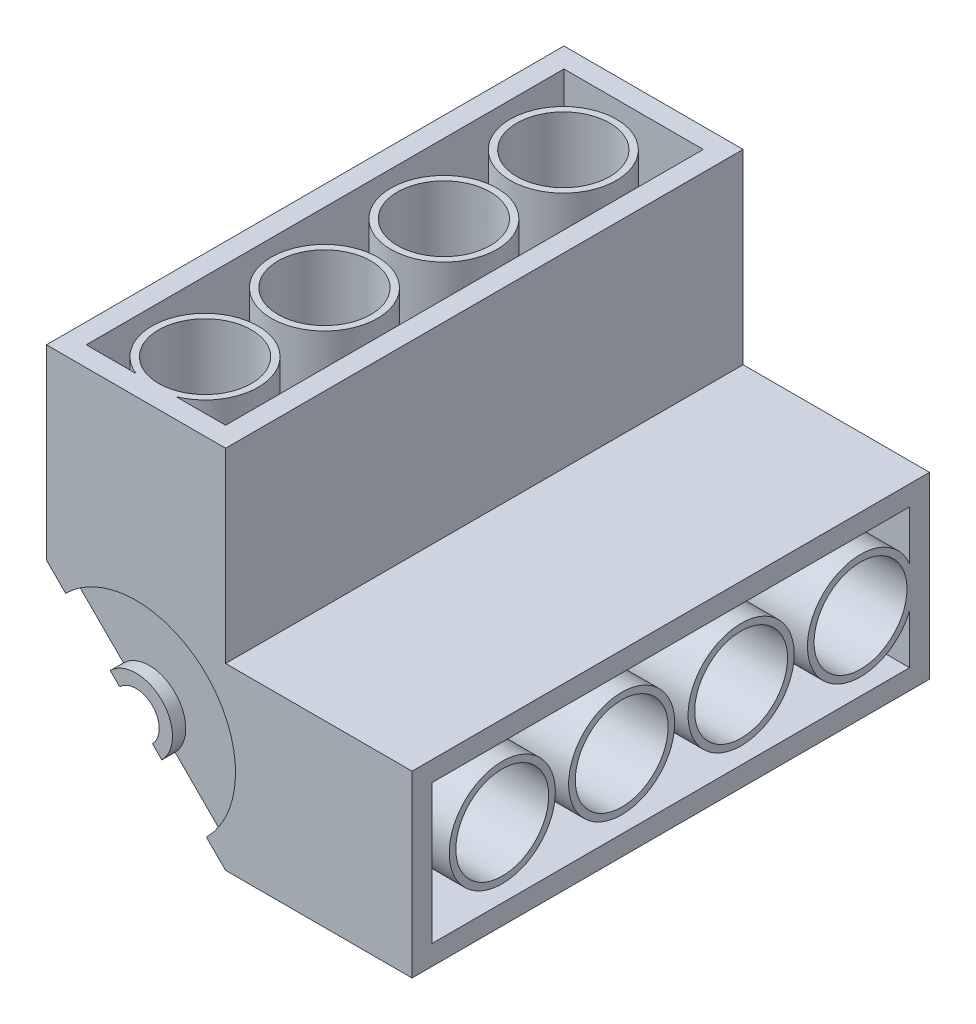
SolidWorks part; units mm, degrees
ref_plane "Alzado" through (0, 0, 0) normal (0, 0, 1) x (1, 0, 0)
ref_plane "Planta" through (0, 0, 0) normal (0, 1, 0) x (1, 0, 0)
ref_plane "Vista lateral" through (0, 0, 0) normal (1, 0, 0) x (0, 0, -1)
sketch "Croquis1" plane through (0, 0, 0) normal (0, 0, 1) x (1, 0, 0)
  line L0 (-81.5266, -99.9092) -> (138.4734, -99.9092) construction
  line L1 (-67.5, 67.5) -> (-12.3744, 12.3744)
  line L2 (12.3744, -12.3744) -> (67.5, -67.5)
  line L3 (-67.5, 67.5) -> (-67.5, 208)
  line L4 (-67.5, 208) -> (67.5, 208)
  line L5 (67.5, 208) -> (67.5, 67.5)
  line L6 (67.5, 67.5) -> (208, 67.5)
  line L7 (208, 67.5) -> (208, -67.5)
  line L8 (208, -67.5) -> (67.5, -67.5)
  arc A0 (12.3744, -12.3744) -> (-12.3744, 12.3744) centre (0, 0) ccw
  arc A1 (53.033, -53.033) -> (-53.033, 53.033) centre (0, 0) ccw
  arc A2 (19.4454, -19.4454) -> (-19.4454, 19.4454) centre (0, 0) ccw
  dimension "D1" = 35
  dimension "D2" = 55
  dimension "D3" = 150
  dimension "D4" = 45
  dimension "D5" = 208
  dimension "D6" = 135
  dimension "D7" = 275.5
extrude "Saliente-Extruir4" add sketch "Croquis1" along normal blind 390 contours A1 L2 L8 L7 L6 L5 L4 L3 L1 region at (-63.6038, 137.75, 0)
ref_plane "Plano2" through (0, 0, 10) normal (0, 0, -1) x (-1, 0, 0)
extrude "Saliente-Extruir5" add sketch "Croquis1<7>" along normal blind 10 from surface contours A2 L2 A1 L1 region at (24.7221, 24.7221, 0) starting at plane "Plano2"
sketch "Croquis1<7>" plane through (0, 0, 0) normal (0, 0, 1) x (1, 0, 0) same geometry as "Croquis1"
extrude "Saliente-Extruir6" add sketch "Croquis1<8>" along normal blind 30 contours L2 A2 L1 A0 region at (18.976, 18.976, 0)
sketch "Croquis1<8>" plane through (0, 0, 0) normal (0, 0, 1) x (1, 0, 0) same geometry as "Croquis1"
pattern_linear "MatrizL1" count 5 spacing 90 along (0, 0, 1) of "Saliente-Extruir5", "Saliente-Extruir6"
sketch "Croquis6" plane through (208, 0, 0) normal (1, 0, 0) x (0, 0, -1)
  line L0 (-390, 67.5) -> (0, 67.5) construction
  line L1 (-375, -52.5) -> (-15, -52.5)
  line L2 (-375, -52.5) -> (-375, 52.5)
  line L3 (-375, 52.5) -> (-15, 52.5)
  line L4 (-15, -52.5) -> (-15, 52.5)
  line L5 (-375, -52.5) -> (-15, 52.5) construction
  line L6 (-375, 52.5) -> (-15, -52.5) construction
  line L7 (0, 67.5) -> (0, -67.5) construction
  point P0 (-195, 0)
  dimension "D1" = 105
  dimension "D2" = 360
  dimension "D3" = 15
  dimension "D4" = 15
extrude "Cortar-Extruir2" cut sketch "Croquis6" against normal blind 120
sketch "Croquis8" plane through (208, 0, 0) normal (1, 0, 0) x (0, 0, -1)
  line L0 (-390, 0) -> (-338, 0) construction
  line L2 (-390, 67.5) -> (-390, -67.5) construction
  circle A0 centre (-338, 0) radius 40
  circle A1 centre (-338, 0) radius 35
  dimension "D2" = 80
  dimension "D3" = 70
  dimension "D1" = 52
ref_plane "Plano4" through (0, 0, 0) normal (0.7071, -0.7071, 0) x (0, 0, -1)
mirror "Simetría2" about plane through (0, 0, 0) normal (0.7071, -0.7071, 0) of "Cortar-Extruir2"
sketch "Croquis16" plane through (208, 0, 0) normal (1, 0, 0) x (0, 0, -1)
  line L0 (0, 67.5) -> (0, -67.5) construction
  circle A0 centre (-52, 0) radius 35
  dimension "D2" = 70
  dimension "D1" = 52
extrude "Cortar-Extruir7" cut sketch "Croquis16" against normal up to surface (133 mm away) up to face at (26.5165, 26.5165, 60)
sketch "Croquis17" plane through (208, 0, 0) normal (1, 0, 0) x (0, 0, -1)
  circle A0 centre (-52, 0) radius 40
  circle A1 centre (-52, 0) radius 35 construction
  circle A2 centre (-52, 0) radius 35
  dimension "D1" = 80
extrude "Saliente-Extruir10" add sketch "Croquis17" against normal up to next (120 mm away)
sketch "Croquis18" plane through (0, 208, 0) normal (0, 1, 0) x (1, 0, 0)
  line L0 (-67.5, -390) -> (67.5, -390) construction
  circle A0 centre (0, -338) radius 35
  point P2 (0, -390)
  dimension "D2" = 70
  dimension "D1" = 52
extrude "Cortar-Extruir8" cut sketch "Croquis18" against normal up to surface (133 mm away) up to face at (26.5165, 26.5165, 330)
sketch "Croquis19" plane through (0, 208, 0) normal (0, 1, 0) x (1, 0, 0)
  circle A0 centre (0, -338) radius 40
  circle A1 centre (0, -338) radius 35 construction
  circle A2 centre (0, -338) radius 35
  dimension "D1" = 80
extrude "Saliente-Extruir11" add sketch "Croquis19" against normal up to next (120 mm away)
pattern_linear "MatrizL7" count 4 spacing 90 along (0, 0, -1) of "Saliente-Extruir11", "Cortar-Extruir8"
pattern_linear "MatrizL10" count 4 spacing 90 along (0, 0, 1) of "Cortar-Extruir7", "Saliente-Extruir10"
